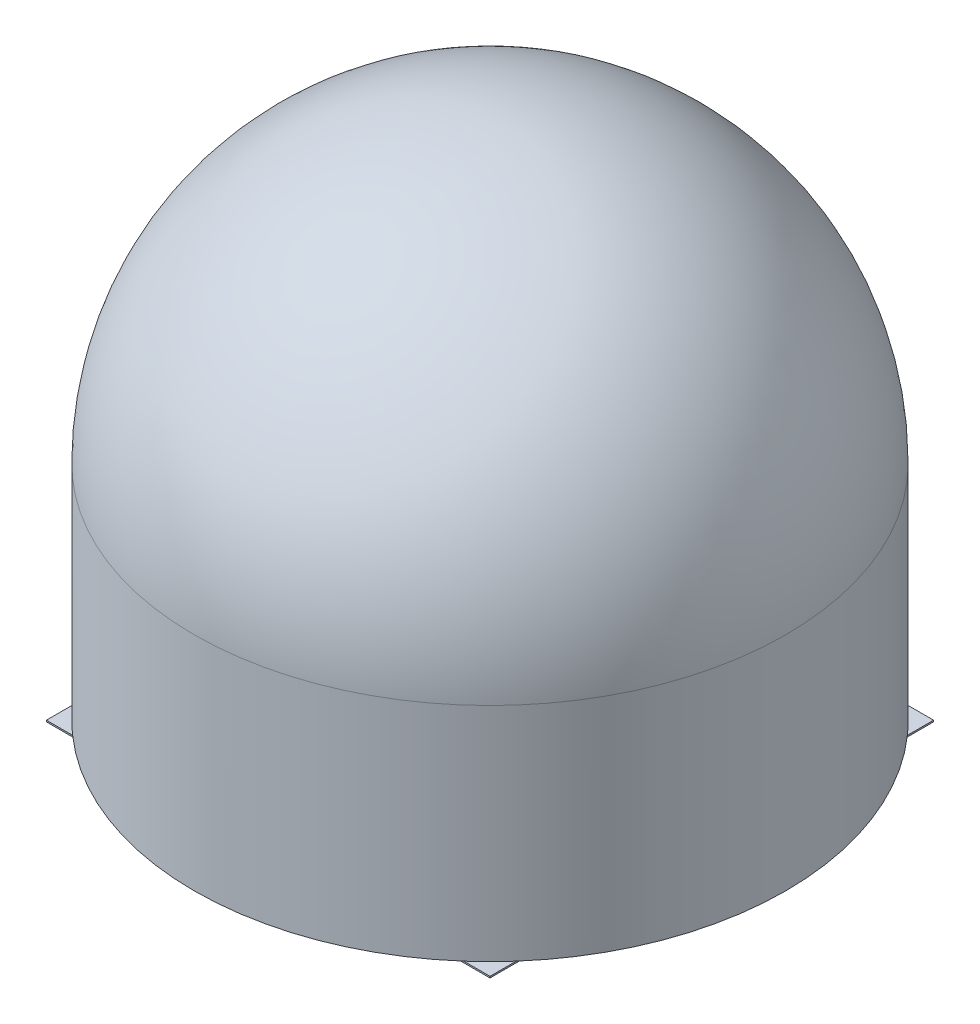
SolidWorks part; units mm, degrees
ref_plane "Front Plane" through (0, 0, 0) normal (0, 0, 1) x (1, 0, 0)
ref_plane "Top Plane" through (0, 0, 0) normal (0, 1, 0) x (1, 0, 0)
ref_plane "Right Plane" through (0, 0, 0) normal (1, 0, 0) x (0, 0, -1)
sketch "Sketch2" plane through (0, 0, 0) normal (0, 1, 0) x (1, 0, 0)
  line L5 (125, -125) -> (-125, 125) construction
  line L6 (125, 125) -> (-125, -125) construction
  line L11 (150, -150) -> (-141.4214, 141.4214) construction
  line L12 (150, 150) -> (-150, -150) construction
  circle A0 centre (0, 0) radius 200
  point P0 (0, 0)
  point P6 (0, 0)
extrude "Boss-Extrude1" add sketch "Sketch2" along normal blind 150 contours A0
dome "Dome2" faces to dome 1 distance 200 reverse direction no elliptical dome no face at (0, 150, 200) parameters "D1"=200
sketch "Sketch4" plane through (0, 0, 0) normal (0, -1, 0) x (1, 0, 0)
  line L1 (-150, 150) -> (150, 150)
  line L2 (-150, 150) -> (-150, -150)
  line L3 (-150, -150) -> (150, -150)
  line L4 (150, 150) -> (150, -150)
  line L5 (-150, 150) -> (150, -150) construction
  line L6 (-150, -150) -> (150, 150) construction
  point P0 (0, 0)
  dimension "D1" = 300
  dimension "D2" = 300
extrude "Boss-Extrude2" add sketch "Sketch4" along normal blind 1
